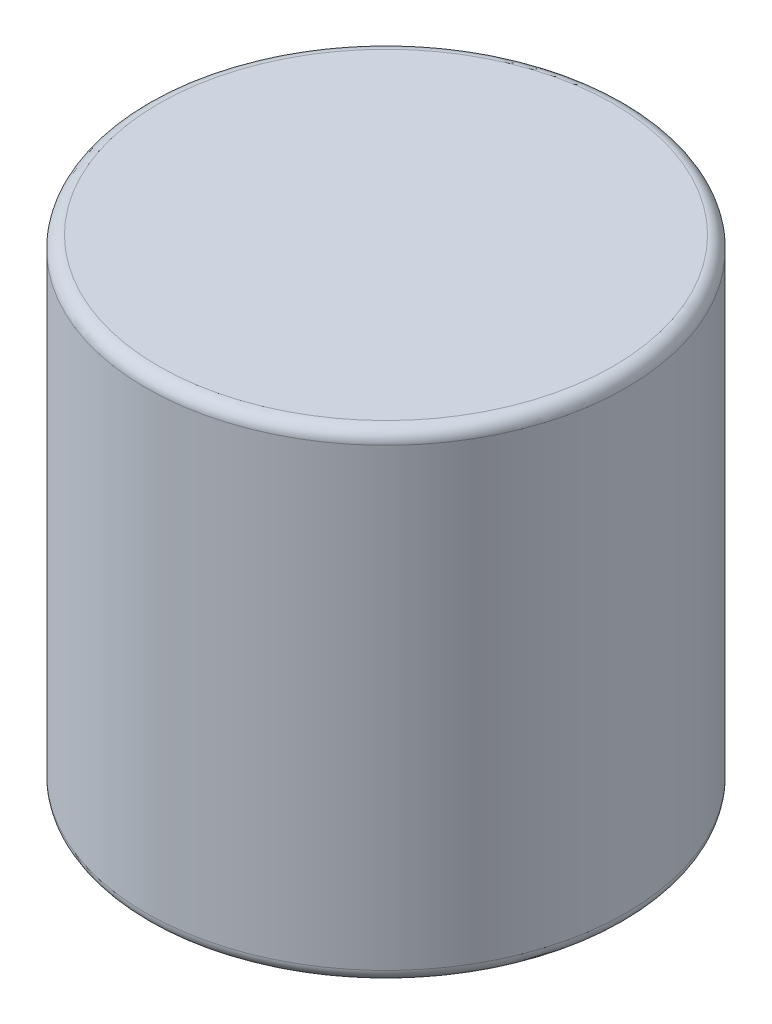
SolidWorks part; units mm, degrees
ref_plane "Front Plane" through (0, 0, 0) normal (0, 0, 1) x (1, 0, 0)
ref_plane "Top Plane" through (0, 0, 0) normal (0, 1, 0) x (1, 0, 0)
ref_plane "Right Plane" through (0, 0, 0) normal (1, 0, 0) x (0, 0, -1)
sketch "Sketch1" plane through (0, 0, 0) normal (0, 1, 0) x (1, 0, 0)
  circle A0 centre (0, 0) radius 4.7625
  dimension "D1" = 9.525
extrude "Boss-Extrude1" add sketch "Sketch1" along normal blind 9.525
fillet "Fillet1" radius 0.25 2 edges at (0, 0, 4.7625) (0, 9.525, 4.7625)
